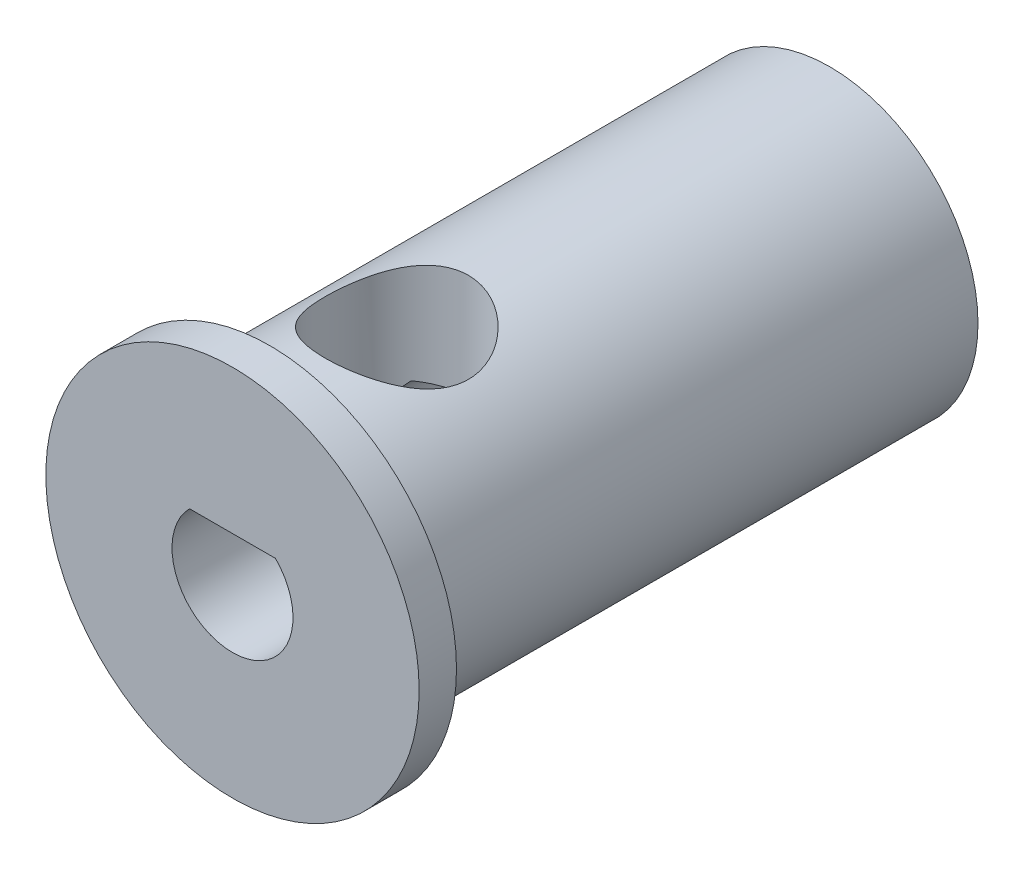
SolidWorks part; units mm, degrees
material "PLA2"
ref_plane "Front Plane" through (0, 0, 0) normal (0, 0, 1) x (1, 0, 0)
ref_plane "Top Plane" through (0, 0, 0) normal (0, 1, 0) x (1, 0, 0)
ref_plane "Right Plane" through (0, 0, 0) normal (1, 0, 0) x (0, 0, -1)
sketch "Sketch2" plane through (0, 0, 0) normal (0, 0, 1) x (1, 0, 0)
  circle A1 centre (0, 0) radius 5.0419
  circle A2 centre (0, 0) radius 2.0574
  dimension "D1" = 4.1148
  dimension "D3" = 10.0838
extrude "Boss-Extrude1" add sketch "Sketch2" along normal blind 19.05
sketch "Sketch6" plane through (0, 0, 0) normal (0, 0, -1) x (-1, 0, 0)
  line L1 (1.4618, 1.4478) -> (-1.4618, 1.4478)
  line L2 (0, 1.4478) -> (0, -2.0574) construction
  arc A3 (1.4618, 1.4478) -> (-1.4618, 1.4478) centre (0, 0) ccw
  circle A4 centre (0, 0) radius 2.0574 construction
  dimension "D1" = 3.5052
extrude "Boss-Extrude2" add sketch "Sketch6" against normal up to surface (19.05 mm away) up to face at (5.0419, 0, 19.05)
sketch "Sketch3" plane through (0, 0, 0) normal (0, -1, 0) x (1, 0, 0)
  line L0 (0, 14.732) -> (0, 0) construction
  line L1 (-5.0419, 9.525) -> (5.0419, 9.525) construction
  line L2 (-5.0419, 19.05) -> (-5.0419, 0) construction
  line L3 (5.0419, 0) -> (5.0419, 19.05) construction
  line L4 (5.0419, 19.05) -> (-5.0419, 19.05) construction
  circle A0 centre (0, 14.732) radius 2.4384
  dimension "D1" = 4.8768
  dimension "D2" = 4.318
extrude "Cut-Extrude1" cut sketch "Sketch3" against normal mid plane 25.4
sketch "Sketch4" plane through (0, 0, 0) normal (1, 0, 0) x (0, 0, -1)
  line L1 (0, 0) -> (50000, 0) construction
  line L2 (-19.05, 0) -> (-19.05, 6.35)
  line L3 (-19.05, 6.35) -> (-20.32, 6.35)
  line L4 (-20.32, 6.35) -> (-20.32, 0)
  line L5 (-20.32, 0) -> (-19.05, 0)
  line L6 (-19.05, 5.0419) -> (-19.05, -5.0419) construction
  dimension "D1" = 1.27
  dimension "D2" = 12.7
revolve "Revolve1" add sketch "Sketch4" angle 360 about L1
sketch "Sketch5" plane through (0, 0, 19.05) normal (0, 0, -1) x (-1, 0, 0)
  line L1 (1.4618, 1.4478) -> (-1.4618, 1.4478)
  line L2 (1.4618, 1.4478) -> (-1.4618, 1.4478)
  arc A1 (-1.4618, 1.4478) -> (1.4618, 1.4478) centre (0, 0) ccw
  arc A2 (-1.4618, 1.4478) -> (1.4618, 1.4478) centre (0, 0) ccw
  dimension "D1" = 0
extrude "Cut-Extrude2" cut sketch "Sketch5" against normal through all
